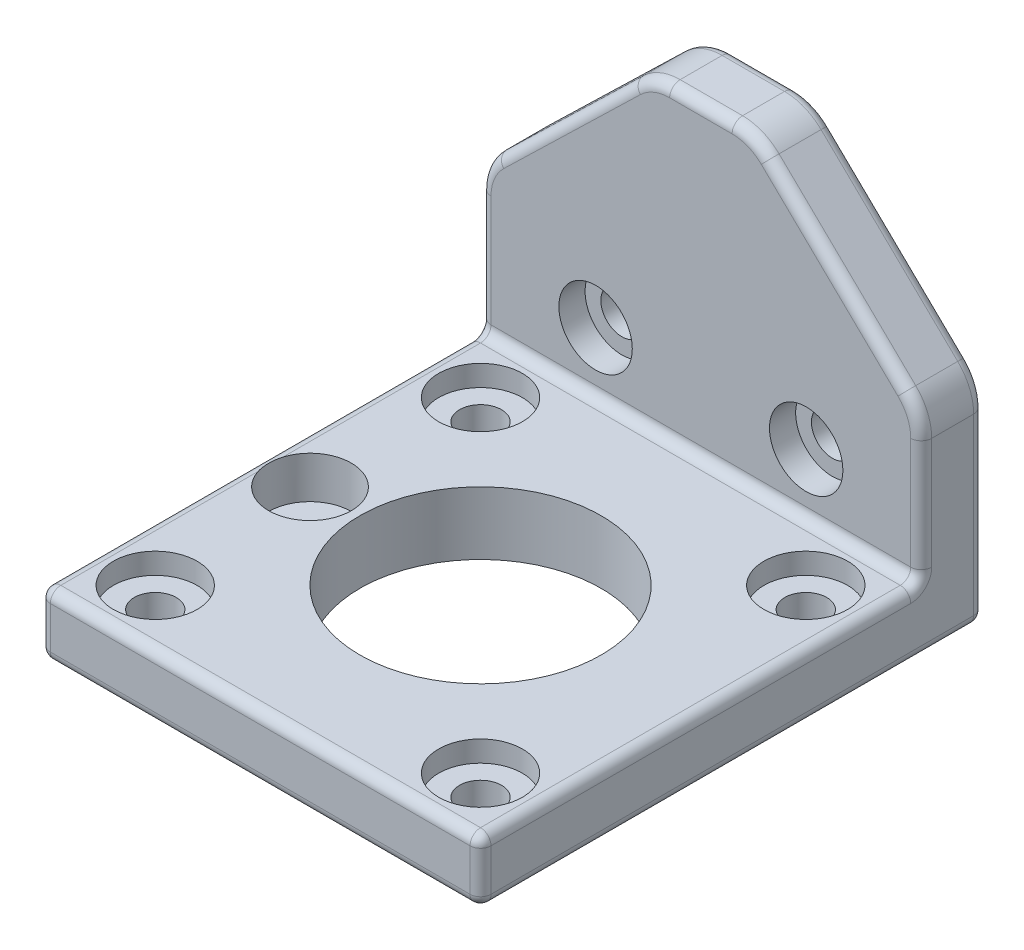
SolidWorks part; units mm, degrees
ref_plane "Front Plane" through (0, 0, 0) normal (0, 0, 1) x (1, 0, 0)
ref_plane "Top Plane" through (0, 0, 0) normal (0, 1, 0) x (1, 0, 0)
ref_plane "Right Plane" through (0, 0, 0) normal (1, 0, 0) x (0, 0, -1)
sketch "Sketch1" plane through (0, 0, 0) normal (0, 1, 0) x (1, 0, 0)
  line L1 (-21, 21) -> (21, 21)
  line L2 (-21, 21) -> (-21, -21)
  line L3 (-21, -21) -> (21, -21)
  line L4 (21, 21) -> (21, -21)
  line L5 (-21, 21) -> (21, -21) construction
  line L6 (-21, -21) -> (21, 21) construction
  point P0 (0, 0)
  dimension "D1" = 42
  dimension "D2" = 42
extrude "Boss-Extrude1" add sketch "Sketch1" along normal blind 6
sketch "Sketch3" plane through (0, 6, 0) normal (0, 1, 0) x (1, 0, 0)
  line L0 (0, -15.5) -> (0, 15.5) construction
  line L1 (-15.5, 0) -> (15.5, 0) construction
  line L2 (-15.5, 15.5) -> (15.5, 15.5) construction
  line L3 (15.5, 15.5) -> (15.5, -15.5) construction
  line L4 (15.5, -15.5) -> (-15.5, -15.5) construction
  line L5 (-15.5, -15.5) -> (-15.5, 15.5) construction
  circle A0 centre (-15.5, 15.5) radius 3.9905
  circle A1 centre (15.5, 15.5) radius 3.9905
  circle A2 centre (-15.5, -15.5) radius 3.9905
  circle A3 centre (15.5, -15.5) radius 3.9905
  point P12 (0, 0)
  point P16 (0, 0)
  point P17 (0, 15.5)
  point P20 (15.5, 0)
  dimension "D1" = 7.981
  dimension "D2" = 31
  dimension "D3" = 31
extrude "Cut-Extrude1" cut sketch "Sketch3" against normal blind 2
sketch "Sketch4" plane through (0, 6, 0) normal (0, 1, 0) x (1, 0, 0)
  circle A0 centre (0, 0) radius 11.5
  circle A1 centre (15.5, 15.5) radius 2
  circle A2 centre (-15.5, 15.5) radius 2
  circle A3 centre (-15.5, -15.5) radius 2
  circle A4 centre (15.5, -15.5) radius 2
  dimension "D1" = 4
  dimension "D2" = 23
extrude "Cut-Extrude2" cut sketch "Sketch4" against normal through all
sketch "Sketch5" plane through (0, 0, -21) normal (0, 0, -1) x (-1, 0, 0)
  line L0 (0, 9.875) -> (0, 19.75) construction
  line L2 (-21, 19.75) -> (-21, 0)
  line L3 (-21, 0) -> (21, 0)
  line L4 (21, 19.75) -> (21, 0)
  line L5 (-21, 19.75) -> (21, 0) construction
  line L6 (-21, 0) -> (21, 19.75) construction
  line L7 (-5, 35.25) -> (5, 35.25)
  line L13 (5, 35.25) -> (21, 19.75)
  line L14 (-5, 35.25) -> (-21, 19.75)
  point P0 (0, 9.875)
  point P6 (0, 27.5)
  dimension "D1" = 35.25
  dimension "D2" = 19.75
  dimension "D3" = 16
  dimension "D4" = 16
  dimension "D5" = 15.5
extrude "Boss-Extrude2" add sketch "Sketch5" along normal blind 6
sketch "Sketch6" plane through (0, 0, -21) normal (0, 0, 1) x (1, 0, 0)
  line L0 (-10.035, 11.75) -> (10.035, 11.75) construction
  line L1 (0, 11.75) -> (0, 0) construction
  circle A0 centre (-10.035, 11.75) radius 3.5
  circle A1 centre (10.035, 11.75) radius 3.5
  dimension "D1" = 7
  dimension "D2" = 7
  dimension "D3" = 11.75
  dimension "D4" = 20.07
extrude "Cut-Extrude3" cut sketch "Sketch6" against normal blind 2.5
sketch "Sketch7" plane through (0, 0, -21) normal (0, 0, 1) x (1, 0, 0)
  circle A0 centre (-10.035, 11.75) radius 2
  circle A1 centre (10.035, 11.75) radius 2
  dimension "D1" = 4
extrude "Cut-Extrude4" cut sketch "Sketch7" against normal through all
fillet "Fillet1" radius 5 4 edges at (21, 19.75, -24) (5, 35.25, -24) (-5, 35.25, -24) (-21, 19.75, -24)
sketch "Sketch8" plane through (0, 6, 0) normal (0, 1, 0) x (1, 0, 0)
  line L0 (0, 0) -> (-16.25, 0) construction
  circle A0 centre (-16.25, 0) radius 3.9365
  dimension "D1" = 7.873
  dimension "D2" = 16.25
extrude "Cut-Extrude5" cut sketch "Sketch8" against normal blind 4
fillet "Fillet2" radius 1 28 edges at (0, 35.25, -21) (4.852, 34.8844, -21) (-4.852, 34.8844, -21) (12.9666, 27.5323, -21) (-12.9666, 27.5323, -21) (20.6041, 19.5823, -21) (-20.6041, 19.5823, -21) (21, 11.8161, -21) (-21, 11.8161, -21) (-21, 8.8161, -27) (-20.6041, 19.5823, -27) (-12.9666, 27.5323, -27) (-4.852, 34.8844, -27) (21, 8.8161, -27) (20.6041, 19.5823, -27) (12.9666, 27.5323, -27) (4.852, 34.8844, -27) (0, 0, -27) (0, 35.25, -27) (0, 6, -21) (0, 0, 21) (0, 6, 21) (21, 0, -3) (21, 6, 0) (-21, 0, -3) (-21, 6, 0) (-21, 3, 21) (21, 3, 21)
